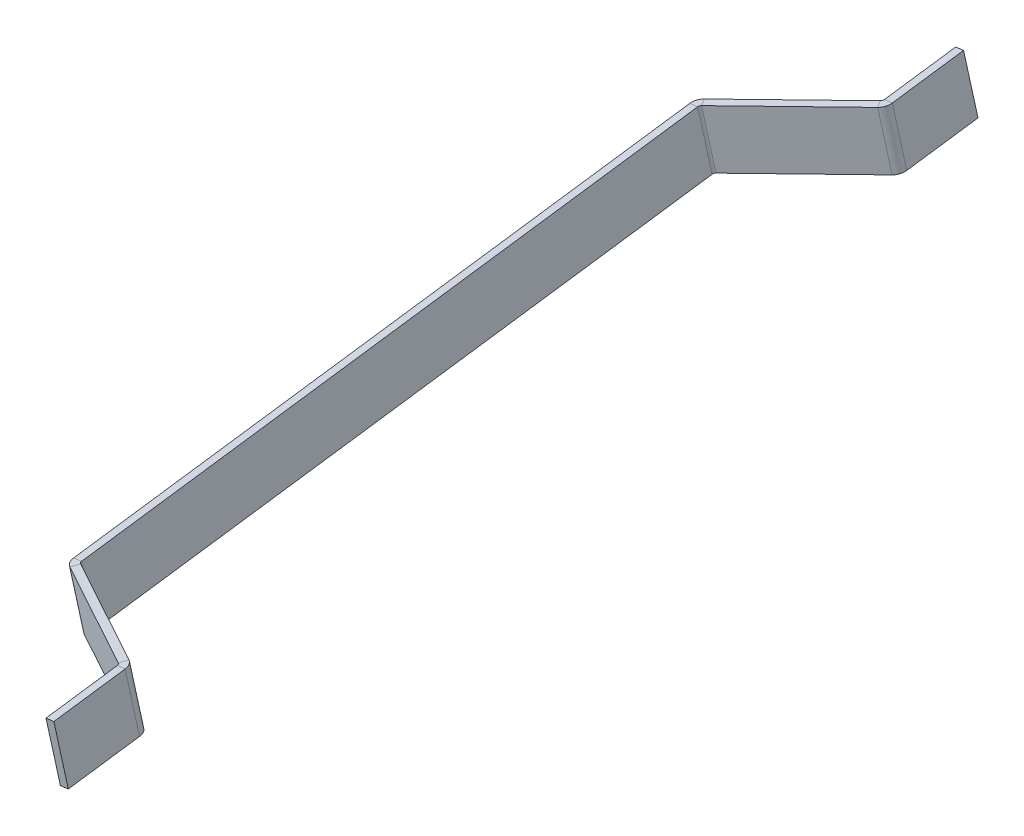
SolidWorks part; units mm, degrees
note: The reader was unsure of these and kept them because the rebuilt part matched: flange length of "Edge-Flange1", "Edge-Flange2", "Edge-Flange3", "Edge-Flange4".
ref_plane "Front Plane" through (0, 0, 0) normal (0, 0, 1) x (1, 0, 0)
ref_plane "Top Plane" through (0, 0, 0) normal (0, 1, 0) x (1, 0, 0)
ref_plane "Right Plane" through (0, 0, 0) normal (1, 0, 0) x (0, 0, -1)
ref_plane "Plane1" through (48.1307, 5.9097, 0) normal (-0.9925, -0.1219, 0) x (0.0149, -0.121, 0.9925)
sketch "Sketch2" plane through (48.1307, 5.9097, 0) normal (-0.9925, -0.1219, 0) x (0.0149, -0.121, 0.9925)
  line L0 (0, 0) -> (0, -83.832) construction
  line L1 (0, 0) -> (170.6945, 0) construction
  line L2 (0, 0) -> (0, -15)
  line L3 (0, -15) -> (160, -15)
  line L4 (160, -15) -> (160, 0)
  line L5 (160, 0) -> (0, 0)
  dimension "D1" = 160
  dimension "D2" = 15
base flange "Base-Flange1" sketch "Sketch2" thickness 2 reverse thickness direction no parameters "D1"=0.7366
edge flange "Edge-Flange1" sketch "Sketch13" flange angle 120 flange length 35 flange position material outside bend radius 0.7366 thickness 2 parameters "D6"=10
sketch "Sketch13" plane through (50.1158, 6.1534, 0) normal (0.5091, -0.0438, 0.8596) x (0.121, -0.9851, -0.1219)
  line L2 (0, 0) -> (0, 33.8453)
  line L3 (0, 33.8453) -> (15, 33.8453)
  line L4 (15, 33.8453) -> (15, 0)
  line L5 (15, 0) -> (0, 0) construction
  line L6 (15, 0) -> (0, 0)
bend "EdgeBend1" bend radius 0.7366 bend angle 60 parameters "D5"=1
edge flange "Edge-Flange2" sketch "Sketch16" flange angle 120 flange length 20 flange position material outside bend radius 0.7366 thickness 2 parameters "D6"=10
sketch "Sketch16" plane through (77.9386, 11.8602, -18.5157) normal (0.9925, 0.1219, 0) x (0.121, -0.9851, -0.1219)
  line L0 (15, 0) -> (0, 0) construction
  line L1 (15, 0) -> (0, 0)
  line L2 (0, 0) -> (0, 18.8453)
  line L3 (0, 18.8453) -> (15, 18.8453)
  line L4 (15, 18.8453) -> (15, 0)
bend "EdgeBend2" bend radius 0.7366 bend angle 60 parameters "D5"=2
edge flange "Edge-Flange3" sketch "Sketch19" flange angle 120 flange length 35 flange position material outside bend radius 0.7366 thickness 2 parameters "D6"=10
sketch "Sketch19" plane through (52.4921, -13.2003, 158.8074) normal (-0.4834, -0.1657, 0.8596) x (0.121, -0.9851, -0.1219)
  line L0 (15, 0) -> (0, 0) construction
  line L1 (15, 0) -> (0, 0)
  line L2 (0, 0) -> (0, 33.8453)
  line L3 (0, 33.8453) -> (15, 33.8453)
  line L4 (15, 33.8453) -> (15, 0)
bend "EdgeBend3" bend radius 0.7366 bend angle 60 parameters "D5"=3
edge flange "Edge-Flange4" sketch "Sketch22" flange angle 120 flange length 20 flange position material outside bend radius 0.7366 thickness 2 parameters "D6"=10
sketch "Sketch22" plane through (80.869, -12.0066, 177.323) normal (0.9925, 0.1219, 0) x (-0.121, 0.9851, 0.1219)
  line L0 (-15, 0) -> (0, 0) construction
  line L1 (-15, 0) -> (0, 0)
  line L2 (-15, 0) -> (-15, 18.8453)
  line L3 (-15, 18.8453) -> (0, 18.8453)
  line L4 (0, 18.8453) -> (0, 0)
bend "EdgeBend4" bend radius 0.7366 bend angle 60 parameters "D5"=4
sketch "Bend-Lines1" [suppressed] plane through (0, 0, 0) normal (0, 1, 0) x (1, 0, 0)
sketch "Bounding-Box1" [suppressed] plane through (0, 0, 0) normal (0, 1, 0) x (1, 0, 0)
sheet metal parameters "Sheet-Metal1" thickness 2 parameters "D1"=0.7366
flat pattern "Flat-Pattern1" [suppressed]
sketch "Bend-Lines2" plane through (0, 0, 0) normal (0, 1, 0) x (1, 0, 0)
sketch3d "Bounding-Box2" [suppressed]
  line L0 (0, -15, 0) -> (-200, -15, 0) construction
  line L1 (0, 0, 0) -> (-200, 0, 0) construction
  line L2 (0, -15, 0) -> (0, 0, 0) construction
  line L3 (-200, -15, 0) -> (-200, 0, 0) construction
sheet metal parameters "Sheet-Metal2" thickness 2 parameters "D1"=0.7366
flat pattern "Flat-Pattern1"
sketch "Bend-Lines2" plane through (0, 0, 25) normal (0, 0, 1) x (1, 0, 0)
  line L0 (-0.484, 0) -> (-0.484, -15) construction
  line L1 (-0.484, 0) -> (-0.484, -15) construction
sketch3d "Bounding-Box2" [suppressed]
  line L0 (-34.8133, -15, 0) -> (200, -15, 0) construction
  line L1 (-34.8133, 0, 0) -> (200, 0, 0) construction
  line L2 (-34.8133, -15, 0) -> (-34.8133, 0, 0) construction
  line L3 (200, -15, 0) -> (200, 0, 0) construction
bend of the flat pattern "Flatten-<EdgeBend1>1"
sheet metal parameters "Sheet-Metal3" thickness 2 parameters "D1"=0.7366
flat pattern "Flat-Pattern1"
sketch "Bend-Lines2" plane through (0, 0, 25) normal (0, 0, 1) x (1, 0, 0)
  line L0 (-0.484, 0) -> (-0.484, -15) construction
  line L1 (-0.484, 0) -> (-0.484, -15) construction
  line L2 (-35.2973, 0) -> (-35.2973, -15) construction
  line L3 (-35.2973, 0) -> (-35.2973, -15) construction
sketch3d "Bounding-Box2" [suppressed]
  line L0 (-54.6266, -15, 0) -> (200, -15, 0) construction
  line L1 (-54.6266, 0, 0) -> (200, 0, 0) construction
  line L2 (-54.6266, -15, 0) -> (-54.6266, 0, 0) construction
  line L3 (200, -15, 0) -> (200, 0, 0) construction
bend of the flat pattern "Flatten-<EdgeBend1>1"
bend of the flat pattern "Flatten-<EdgeBend2>1"
sheet metal parameters "Sheet-Metal4" thickness 2 parameters "D1"=0.7366
flat pattern "Flat-Pattern1"
sketch "Bend-Lines2" plane through (0, 0, 25) normal (0, 0, 1) x (1, 0, 0)
  line L0 (-0.484, 0) -> (-0.484, -15) construction
  line L1 (-0.484, 0) -> (-0.484, -15) construction
  line L2 (-35.2973, 0) -> (-35.2973, -15) construction
  line L3 (-35.2973, 0) -> (-35.2973, -15) construction
  line L4 (200.484, -15) -> (200.484, 0) construction
  line L5 (200.484, -15) -> (200.484, 0) construction
sketch3d "Bounding-Box2" [suppressed]
  line L0 (-54.6266, -15, 0) -> (234.8133, -15, 0) construction
  line L1 (-54.6266, 0, 0) -> (234.8133, 0, 0) construction
  line L2 (-54.6266, -15, 0) -> (-54.6266, 0, 0) construction
  line L3 (234.8133, -15, 0) -> (234.8133, 0, 0) construction
bend of the flat pattern "Flatten-<EdgeBend1>1"
bend of the flat pattern "Flatten-<EdgeBend2>1"
bend of the flat pattern "Flatten-<EdgeBend3>1"
sheet metal parameters "Sheet-Metal5" thickness 2 parameters "D1"=0.7366
flat pattern "Flat-Pattern1"
sketch "Bend-Lines2" plane through (48.1307, 5.9097, 0) normal (-0.9925, -0.1219, 0) x (0, 0, 1)
  line L0 (-0.4804, 0.059) -> (-2.3084, -14.8292) construction
  line L1 (-0.4804, 0.059) -> (-2.3084, -14.8292) construction
  line L2 (-35.0342, 4.3017) -> (-36.8623, -10.5865) construction
  line L3 (-35.0342, 4.3017) -> (-36.8623, -10.5865) construction
  line L4 (157.4597, -34.4463) -> (159.2878, -19.5581) construction
  line L5 (157.4597, -34.4463) -> (159.2878, -19.5581) construction
  line L6 (192.0136, -38.6889) -> (193.8416, -23.8008) construction
  line L7 (192.0136, -38.6889) -> (193.8416, -23.8008) construction
sketch3d "Bounding-Box2" [suppressed]
  line L0 (-56.0475, -8.2309, 0) -> (211.1988, -41.0446, 0) construction
  line L1 (-54.2194, 6.6573, 0) -> (213.0268, -26.1564, 0) construction
  line L2 (-56.0475, -8.2309, 0) -> (-54.2194, 6.6573, 0) construction
  line L3 (211.1988, -41.0446, 0) -> (213.0268, -26.1564, 0) construction
bend of the flat pattern "Flatten-<EdgeBend1>1"
bend of the flat pattern "Flatten-<EdgeBend2>1"
bend of the flat pattern "Flatten-<EdgeBend3>1"
bend of the flat pattern "Flatten-<EdgeBend4>1"
